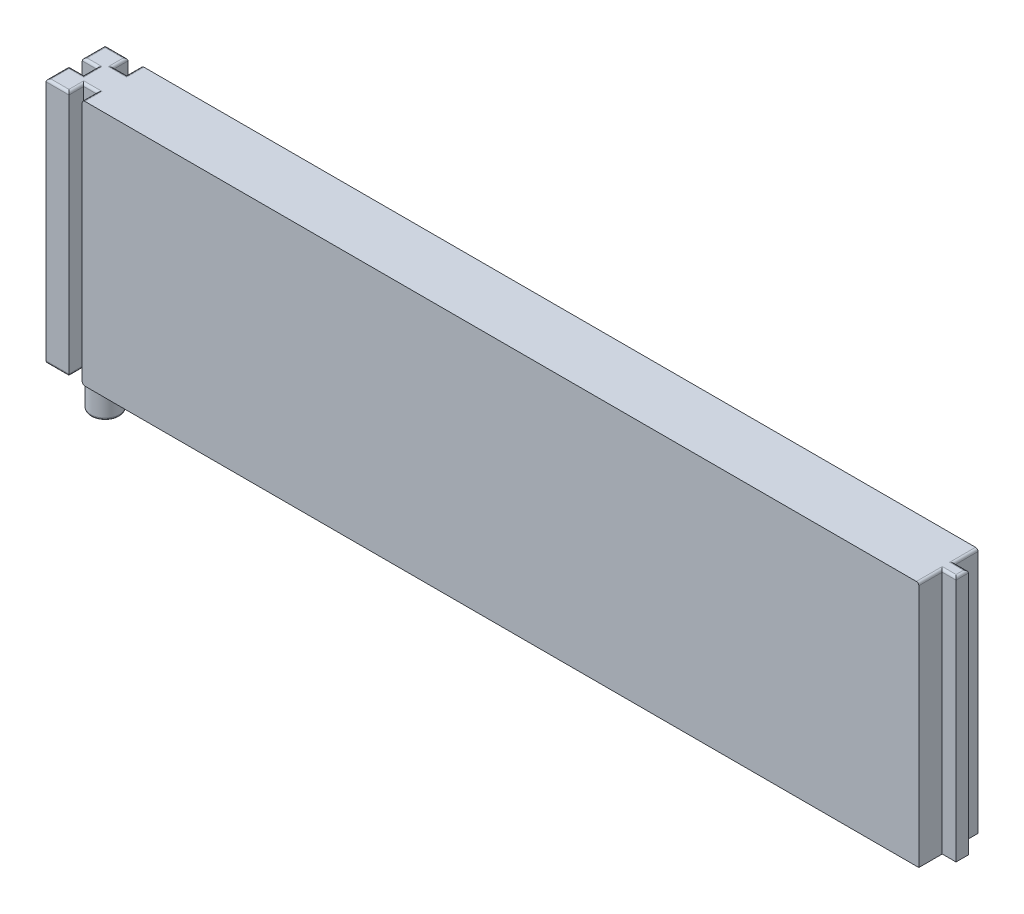
SolidWorks part; units mm, degrees
ref_plane "Plano frontal" through (0, 0, 0) normal (0, 0, 1) x (1, 0, 0)
ref_plane "Plano superior" through (0, 0, 0) normal (0, 1, 0) x (1, 0, 0)
ref_plane "Plano direito" through (0, 0, 0) normal (1, 0, 0) x (0, 0, -1)
sketch "Esboço2" plane through (0, 0, 0) normal (0, 1, 0) x (1, 0, 0)
  circle A0 centre (0, 0) radius 2.9
  dimension "D1" = 5.8
extrude "Ressalto-extrusão1" add sketch "Esboço2" along normal blind 8
fillet "Filete1" radius 0.5 1 edges at (0, 0, 2.9)
sketch "Esboço3" plane through (0, 8, 0) normal (0, 1, 0) x (1, 0, 0)
  line L1 (-6, 6) -> (6, 6)
  line L2 (-6, 6) -> (-6, -6)
  line L3 (-6, -6) -> (6, -6)
  line L4 (6, 6) -> (6, -6)
  line L5 (-6, 6) -> (6, -6) construction
  line L6 (-6, -6) -> (6, 6) construction
  point P0 (0, 0)
  dimension "D1" = 12
  dimension "D2" = 12
extrude "Ressalto-extrusão2" add sketch "Esboço3" along normal blind 50
sketch "Esboço4" plane through (0, 58, 0) normal (0, 1, 0) x (1, 0, 0)
  line L1 (6, 6) -> (-6, 6) construction
  line L2 (-1.35, 6) -> (-1.35, 3)
  line L3 (1.35, 6) -> (1.35, 3)
  line L4 (-1.35, 6) -> (1.35, 6)
  line L5 (1.35, 3) -> (-1.35, 3)
  line L6 (-10.8792, 0) -> (8.9125, 0) construction
  line L34 (1.35, -6) -> (1.35, -3)
  line L35 (-1.35, -3) -> (1.35, -3)
  line L36 (-1.35, -6) -> (-1.35, -3)
  line L37 (1.35, -6) -> (-1.35, -6)
  line L38 (-6, -1.35) -> (-3, -1.35)
  line L39 (-3, 1.35) -> (-3, -1.35)
  line L40 (-6, 1.35) -> (-3, 1.35)
  line L41 (-6, -1.35) -> (-6, 1.35)
  line L42 (6, 1.35) -> (3, 1.35) [skipped]
  line L43 (3, -1.35) -> (3, 1.35) [skipped]
  line L44 (6, -1.35) -> (3, -1.35) [skipped]
  line L45 (6, 1.35) -> (6, -1.35) [skipped]
  point P25 (0, 0)
  point P26 (0, 0)
  point P27 (0, 0)
  point P28 (0, 0.014)
  point P29 (0, 0)
  dimension "D1" = 4.65
  dimension "D2" = 2.7
  dimension "D3" = 3
  dimension "D4" = 4
extrude "Corte-extrusão1" cut sketch "Esboço4" against normal blind 50
fillet "Filete13" radius 0.5 13 edges at (1.35, 58, 4.5) (0, 58, 3) (-1.35, 58, 4.5) (-3.675, 58, 6) (-6, 58, 3.675) (-4.5, 58, 1.35) (-3, 58, 0) (1.35, 58, -4.5) (0, 58, -3) (-4.5, 58, -1.35) (-1.35, 58, -4.5) (-3.675, 58, -6) (-6, 58, -3.675)
fillet "Filete14" radius 0.5 13 edges at (0, 8, -3) (1.35, 8, 4.5) (0, 8, 3) (-1.35, 8, 4.5) (-3.675, 8, 6) (-6, 8, 3.675) (-4.5, 8, 1.35) (-3, 8, 0) (1.35, 8, -4.5) (-4.5, 8, -1.35) (-1.35, 8, -4.5) (-3.675, 8, -6) (-6, 8, -3.675)
sketch "Esboço5" plane through (6, 0, 0) normal (1, 0, 0) x (0, 0, -1)
  line L0 (-6, 8) -> (-6, 58)
  line L1 (-6, 58) -> (6, 58)
  line L2 (6, 58) -> (6, 8)
  line L3 (6, 8) -> (-6, 8)
extrude "Ressalto-extrusão3" add sketch "Esboço5" along normal blind 167.8
sketch "Esboço7" plane through (0, 58, 0) normal (0, 1, 0) x (1, 0, 0)
  line L0 (173.8, 6) -> (173.8, 1.25)
  line L1 (173.8, 6) -> (173.8, -6) construction
  line L2 (173.8, 1.25) -> (171, 1.25)
  line L3 (171, 1.25) -> (171, 6)
  line L4 (173.8, 6) -> (1.85, 6) construction
  line L5 (171, 6) -> (173.8, 6)
  line L6 (173.8, -6) -> (173.8, -1.25)
  line L7 (173.8, -1.25) -> (171, -1.25)
  line L8 (171, -1.25) -> (171, -6)
  line L9 (1.85, -6) -> (173.8, -6) construction
  line L10 (171, -6) -> (173.8, -6)
  dimension "D1" = 2.8
  dimension "D2" = 2.8
  dimension "D3" = 4.75
  dimension "D4" = 4.75
extrude "Corte-extrusão2" cut sketch "Esboço7" against normal blind 50
fillet "Filete16" radius 0.5 5 edges at (171, 58, -3.625) (171, 58, 3.625) (172.4, 58, -1.25) (173.8, 58, 0) (172.4, 58, 1.25)
